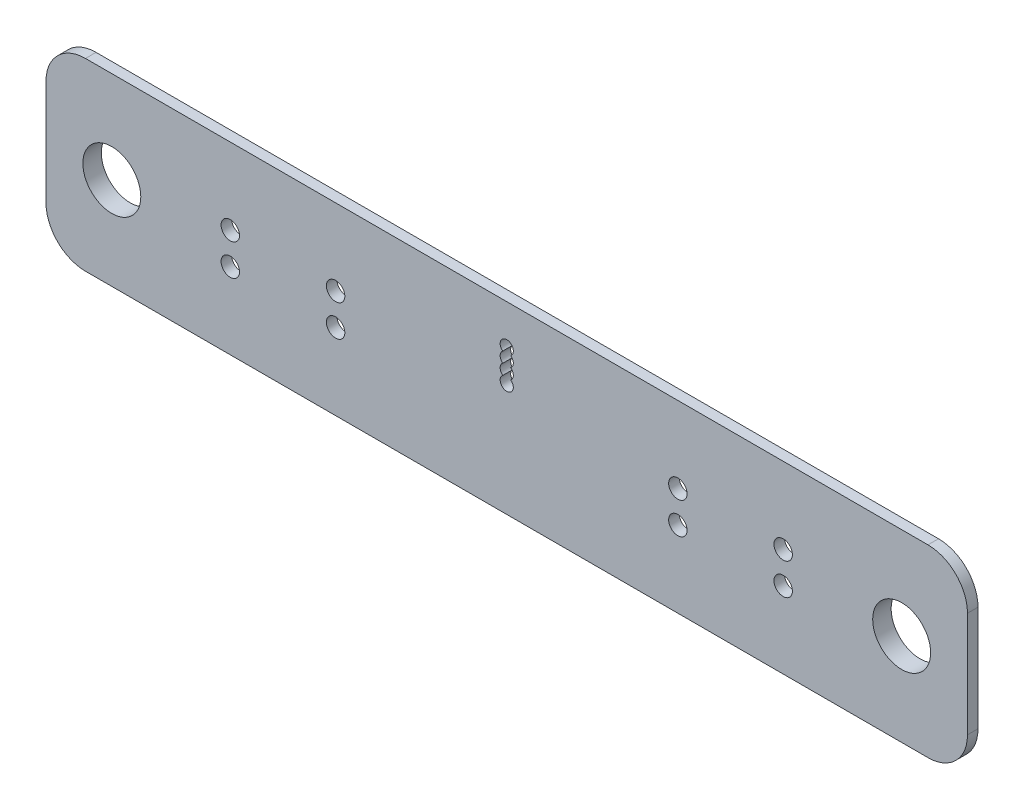
SolidWorks part; units mm, degrees
ref_plane "Ön Düzlem" through (0, 0, 0) normal (0, 0, 1) x (1, 0, 0)
ref_plane "Üst Düzlem" through (0, 0, 0) normal (0, 1, 0) x (1, 0, 0)
ref_plane "Sağ Düzlem" through (0, 0, 0) normal (1, 0, 0) x (0, 0, -1)
sketch "Sketch1" plane through (0, 0, 0) normal (0, 0, 1) x (1, 0, 0)
  line L1 (-175, 35) -> (175, 35)
  line L2 (-175, 35) -> (-175, -35)
  line L3 (-175, -35) -> (175, -35)
  line L4 (175, 35) -> (175, -35)
  line L5 (-175, 35) -> (175, -35) construction
  line L6 (-175, -35) -> (175, 35) construction
  point P0 (0, 0)
  dimension "D1" = 70
  dimension "D2" = 350
extrude "Boss-Extrude1" add sketch "Sketch1" along normal blind 4
fillet "Fillet1" radius 15 4 edges at (175, -35, 2) (175, 35, 2) (-175, -35, 2) (-175, 35, 2)
sketch "Sketch2" plane through (0, 0, 0) normal (0, 0, -1) x (-1, 0, 0)
  line L0 (-175, -20) -> (-175, 20) construction
  circle A0 centre (-150, 0) radius 11
  dimension "D1" = 25
  dimension "D2" = 22
extrude "Cut-Extrude1" cut sketch "Sketch2" against normal blind 10
sketch "Sketch3" plane through (0, 0, 0) normal (0, 0, -1) x (-1, 0, 0)
  circle A0 centre (-150, 0) radius 11
  circle A1 centre (-150, 0) radius 13.5
  dimension "D1" = 27
  dimension "D2" = 22
extrude "Boss-Extrude2" add sketch "Sketch3" along normal blind 9
mirror "Mirror2" about plane through (0, 0, 0) normal (1, 0, 0) of "Cut-Extrude1", "Boss-Extrude2"
sketch "Sketch4" plane through (0, 0, 4) normal (0, 0, 1) x (1, 0, 0)
  arc A0 (1.5, 18) -> (-1.5, 18) centre (0, 20) ccw
  arc A1 (-1.5, 18) -> (-1.5, 14) centre (0, 16) ccw
  arc A2 (1.5, 10) -> (1.5, 14) centre (0, 12) ccw
  arc A3 (-1.5, 10) -> (1.5, 10) centre (0, 8) ccw
  arc A4 (1.5, 14) -> (1.5, 18) centre (0, 16) ccw
  arc A5 (-1.5, 14) -> (-1.5, 10) centre (0, 12) ccw
  circle A6 centre (-105, 6) radius 3.5
  circle A7 centre (-105, -6) radius 3.5
  circle A8 centre (-65, -6) radius 3.5
  circle A9 centre (-65, 6) radius 3.5
  circle A10 centre (65, 6) radius 3.5
  circle A11 centre (65, -6) radius 3.5
  circle A12 centre (105, -6) radius 3.5
  circle A13 centre (105, 6) radius 3.5
  circle A14 centre (150, 0) radius 11 construction
  circle A15 centre (-150, 0) radius 11 construction
  dimension "D4" = 12
  dimension "D5" = 12
  dimension "D6" = 12
  dimension "D2" = 12
  dimension "D7" = 6
  dimension "D8" = 6
  dimension "D9" = 45
  dimension "D10" = 40
  dimension "D11" = 6
  dimension "D12" = 45
  dimension "D13" = 40
extrude "Cut-Extrude3" cut sketch "Sketch4" against normal blind 10
sketch "Sketch6" plane through (0, 35, 0) normal (0, 1, 0) x (1, 0, 0)
  line L0 (-175, 0) -> (175, 0)
  line L1 (-175, 0) -> (-175, 10.5244)
  line L2 (175, 0) -> (175, 10.5244)
  line L3 (-175, 10.5244) -> (175, 10.5244)
extrude "Cut-Extrude5" cut sketch "Sketch6" against normal blind 116
sketch "Sketch7" plane through (0, 0, 0) normal (0, 0, -1) x (-1, 0, 0)
  circle A0 centre (-150, 0) radius 11
  circle A1 centre (-150, 0) radius 13.5
  circle A2 centre (150, 0) radius 13.5
  circle A3 centre (150, 0) radius 11
  dimension "D1" = 22
  dimension "D2" = 22
  dimension "D3" = 27
  dimension "D4" = 27
extrude "Boss-Extrude3" add sketch "Sketch7" along normal blind 3
